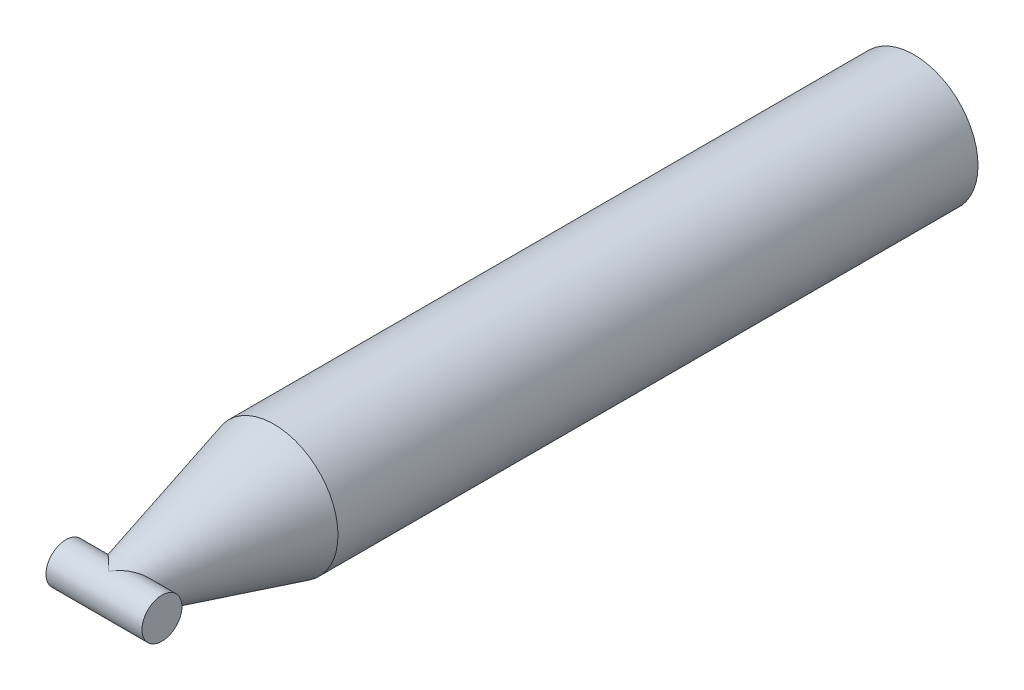
SolidWorks part; units mm, degrees
ref_plane "Front Plane" through (0, 0, 0) normal (0, 0, 1) x (1, 0, 0)
ref_plane "Top Plane" through (0, 0, 0) normal (0, 1, 0) x (1, 0, 0)
ref_plane "Right Plane" through (0, 0, 0) normal (1, 0, 0) x (0, 0, -1)
sketch "Sketch2" plane through (0, 0, 0) normal (1, 0, 0) x (0, 0, -1)
  line L0 (-50, 0) -> (50, 0) construction
  line L1 (50, 0) -> (50, 8)
  line L2 (50, 8) -> (-30, 8)
  line L3 (-30, 8) -> (-50.6528, 2.4133)
  line L4 (-52.5, 0) -> (50, 0)
  arc A0 (-50.6528, 2.4133) -> (-52.5, 0) centre (-50, 0) ccw
  dimension "D1" = 2.5
  dimension "D2" = 8
  dimension "D3" = 80
  dimension "D4" = 100
revolve "Revolve1" add sketch "Sketch2" angle 360 about L0
sketch "Sketch3" plane through (0, 0, 0) normal (1, 0, 0) x (0, 0, -1)
  line L0 (50, -8) -> (50, 8) construction
  circle A0 centre (-50, 0) radius 2.5
  dimension "D1" = 5
  dimension "D2" = 100
extrude "Boss-Extrude1" add sketch "Sketch3" along normal blind 6 and the other way blind 6
